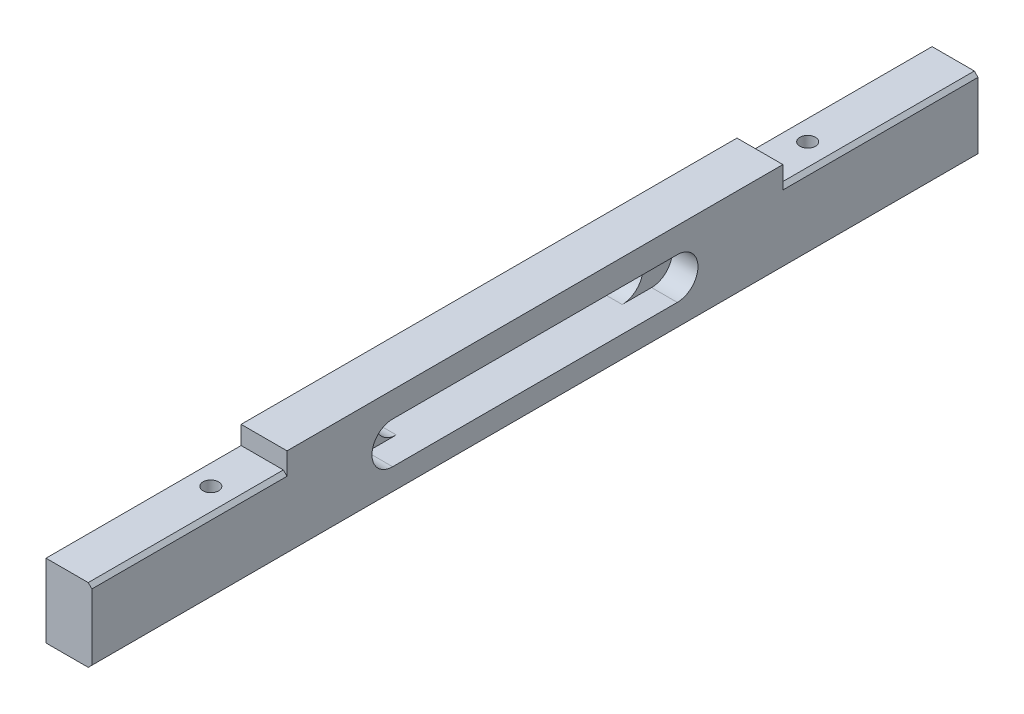
SolidWorks part; units mm, degrees
ref_plane "前视基准面" through (0, 0, 0) normal (0, 0, 1) x (1, 0, 0)
ref_plane "上视基准面" through (0, 0, 0) normal (0, 1, 0) x (1, 0, 0)
ref_plane "右视基准面" through (0, 0, 0) normal (1, 0, 0) x (0, 0, -1)
sketch "草图1" plane through (0, 0, 0) normal (1, 0, 0) x (0, 0, -1)
  line L0 (-15.5, 0) -> (15.5, 0) construction
  line L1 (-27, 5) -> (27, 5)
  line L2 (-27, 5) -> (-27, 3)
  line L3 (-27, -5) -> (27, -5)
  line L4 (27, 5) -> (27, 3)
  line L5 (-27, 5) -> (27, -5) construction
  line L6 (-27, -5) -> (27, 5) construction
  line L7 (-15.5, 2.25) -> (15.5, 2.25)
  line L8 (-15.5, -2.25) -> (15.5, -2.25)
  line L9 (-12.3, 0) -> (12.3, 0) construction
  line L10 (-12.3, 2.25) -> (12.3, 2.25)
  line L11 (-12.3, -2.25) -> (12.3, -2.25)
  line L12 (27, 3) -> (48.25, 3)
  line L13 (-48.25, 3) -> (-27, 3)
  line L14 (-48.25, 3) -> (-48.25, -3)
  line L15 (-48.25, -3) -> (-27, -3)
  line L16 (48.25, 3) -> (48.25, -3)
  line L17 (-48.25, 3) -> (48.25, -3) construction
  line L18 (-48.25, -3) -> (48.25, 3) construction
  line L19 (27, -3) -> (48.25, -3)
  line L20 (-27, -3) -> (-27, -5)
  line L21 (27, -3) -> (27, -5)
  arc A0 (-15.5, 2.25) -> (-15.5, -2.25) centre (-15.5, 0) ccw
  arc A1 (15.5, -2.25) -> (15.5, 2.25) centre (15.5, 0) ccw
  arc A2 (-12.3, 2.25) -> (-12.3, -2.25) centre (-12.3, 0) ccw
  arc A3 (12.3, -2.25) -> (12.3, 2.25) centre (12.3, 0) ccw
  point P0 (0, 0)
  point P8 (0, 0)
  point P14 (0, 0)
  point P20 (0, 0)
  dimension "D1" = 31
  dimension "D2" = 24.6
  dimension "D3" = 4.5
  dimension "D4" = 10
  dimension "D5" = 21.25
  dimension "D6" = 96.5
  dimension "D7" = 6
extrude "凸台-拉伸1" add sketch "草图1" against normal blind 5 contours L2 L13 L14 L15 L20 L3 L21 L19 L16 L12 L4 L1
extrude "切除-拉伸1" cut sketch "草图1<3>" against normal blind 2.8 contours A0 L8 A1 L7
sketch "草图1<3>" plane through (0, 0, 0) normal (1, 0, 0) x (0, 0, -1) same geometry as "草图1"
extrude "切除-拉伸2" cut sketch "草图1<4>" against normal through all contours A2 L11 A3 L10
sketch "草图1<4>" plane through (0, 0, 0) normal (1, 0, 0) x (0, 0, -1) same geometry as "草图1"
sketch "草图6" plane through (0, -3, 0) normal (0, -1, 0) x (1, 0, 0)
  line L0 (0, -48.25) -> (0, -27) construction
  line L1 (0, -27) -> (-5, -27) construction
  line L2 (-5, -27) -> (-5, -48.25) construction
  line L3 (-5, -48.25) -> (0, -48.25) construction
  line L4 (0, 27) -> (0, 48.25) construction
  line L5 (0, 48.25) -> (-5, 48.25) construction
  line L6 (-5, 48.25) -> (-5, 27) construction
  line L7 (-5, 27) -> (0, 27) construction
  line L8 (0, -48.25) -> (0, -27)
  line L9 (0, -27) -> (-5, -27)
  line L10 (-5, -27) -> (-5, -48.25)
  line L11 (-5, -48.25) -> (0, -48.25)
  line L12 (0, 27) -> (0, 48.25)
  line L13 (0, 48.25) -> (-5, 48.25)
  line L14 (-5, 48.25) -> (-5, 27)
  line L15 (-5, 27) -> (0, 27)
extrude "凸台-拉伸2" add sketch "草图6" along normal up to surface (2 mm away) up to face at (-2.5, -5, 0)
sketch "草图5" plane through (0, -5, 0) normal (0, -1, 0) x (1, 0, 0)
  circle A0 centre (-2.8, 32.5) radius 1.2 construction
  circle A2 centre (-2.8, -32.5) radius 1.2 construction
  circle A4 centre (-2.8, 32.5) radius 0.85
  circle A5 centre (-2.8, -32.5) radius 0.85
  point P1 (0, 0)
  point P9 (0, 0)
  dimension "D1" = 1.7
extrude "切除-拉伸4" cut sketch "草图5" against normal through all
chamfer "倒角1" distance 0.4 angle 45 3 edges at (0, 3, 37.625) (0, 3, -37.625) (0, -5, 0)
